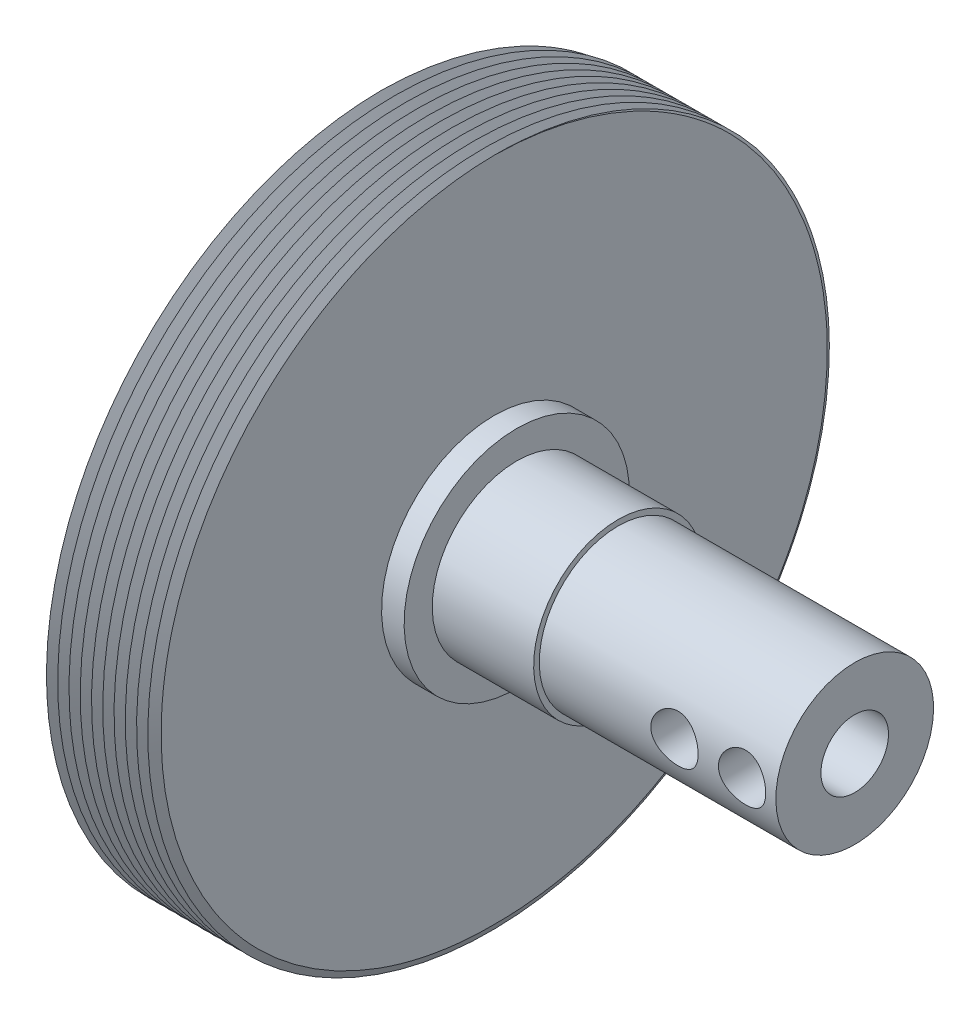
SolidWorks part; units mm, degrees
ref_plane "Front Plane" through (0, 0, 0) normal (0, 0, 1) x (1, 0, 0)
ref_plane "Top Plane" through (0, 0, 0) normal (0, 1, 0) x (1, 0, 0)
ref_plane "Right Plane" through (0, 0, 0) normal (1, 0, 0) x (0, 0, -1)
sketch "Sketch1" plane through (0, 0, 0) normal (0, 0, 1) x (1, 0, 0)
  line L4 (-12.8957, 0) -> (28.1974, 0) construction
  line L5 (0, 0) -> (0, 30)
  line L6 (0, 30) -> (10, 30)
  line L7 (10, 30) -> (10, 10)
  line L8 (10, 10) -> (12, 10)
  line L9 (12, 10) -> (12, 7.5)
  line L10 (12, 7.5) -> (21, 7.5)
  line L13 (42, 7) -> (42, 3)
  line L14 (28.1974, 0) -> (0, 0)
  line L15 (42, 3) -> (30, 3)
  line L16 (30, 3) -> (28.1974, 0)
  line L17 (67.8432, 0) -> (1087.5353, 0) construction
  line L18 (12, 10) -> (11, 10) construction
  line L19 (11, 10) -> (11, 17.5) construction
  line L20 (11, 17.5) -> (10, 17.5) construction
  line L21 (11, 17.5) -> (13, 17.5) construction
  line L22 (13, 17.5) -> (13, 10) construction
  line L23 (13, 10) -> (11, 10) construction
  line L24 (13, 17.5) -> (14, 17.5) construction
  line L25 (14, 17.5) -> (14, 10) construction
  line L26 (14, 10) -> (13, 10) construction
  line L27 (19, 17.5) -> (19, 10) construction
  line L28 (19, 10) -> (20, 10) construction
  line L29 (20, 10) -> (20, 17.5) construction
  line L30 (20, 17.5) -> (19, 17.5) construction
  line L31 (20, 17.5) -> (22, 17.5) construction
  line L32 (22, 17.5) -> (22, 10) construction
  line L33 (22, 10) -> (20, 10) construction
  line L34 (22, 17.5) -> (23, 17.5) construction
  line L35 (23, 17.5) -> (23, 10) construction
  line L36 (23, 10) -> (22, 10) construction
  line L37 (14, 10.5) -> (19, 10.5) construction
  line L38 (14, 7.5) -> (14, 8.5) construction
  line L39 (14, 8.5) -> (19, 8.5) construction
  line L40 (19, 8.5) -> (19, 7.5) construction
  line L41 (14, 9.5) -> (19, 9.5) construction
  line L42 (16.5, 10.5) -> (16.5, 9.5) construction
  line L43 (21, 7.5) -> (21, 7)
  line L44 (21, 7) -> (42, 7)
  line L45 (23, 17.5) -> (29, 17.5) construction
  line L46 (29, 17.5) -> (29, 7) construction
  circle A0 centre (33, 0) radius 2 construction
  circle A1 centre (39, 0) radius 2 construction
  dimension "D21" = 4
  dimension "D1" = 30
  dimension "D2" = 10
  dimension "D3" = 6
  dimension "D4" = 1
  dimension "D5" = 1
  dimension "D6" = 2
  dimension "D7" = 15
  dimension "D8" = 20
  dimension "D9" = 2
  dimension "D10" = 17.5
  dimension "D11" = 10.5
  dimension "D12" = 1
  dimension "D13" = 5
  dimension "D14" = 14
  dimension "D15" = 2
  dimension "D16" = 6
  dimension "D17" = 12
  dimension "D18" = 59
  dimension "D19" = 3
  dimension "D20" = 6
revolve "Revolve1" add sketch "Sketch1" angle 360 about L14
sketch "Sketch2" plane through (0, 0, 0) normal (0, 0, 1) x (1, 0, 0)
  line L0 (0, 30) -> (-0.5, 29.134)
  line L1 (-0.5, 29.134) -> (-1, 30)
  line L2 (-1, 30) -> (-1, 31)
  line L3 (-1, 31) -> (0, 31)
  line L4 (0, 31) -> (0, 30)
  dimension "D1" = 1
  dimension "D2" = 60
  dimension "D3" = 1
sketch "Sketch3" plane through (0, 0, 0) normal (-1, 0, 0) x (0, 0, 1)
  circle A0 centre (0, 0) radius 30 construction
  circle A1 centre (0, 0) radius 30
curve "Helix/Spiral1" pitch 1 height 50 turns 50
sweep "Cut-Sweep1" cut profiles "Sketch2" path "Helix/Spiral1" align with end faces yes
ref_plane "Plane1" through (0, 0, 7) normal (0, 0, 1) x (1, 0, 0)
hole_wizard "M5x0.8 Tapped Hole1" positions "Sketch4" profile "Sketch6" tap size "M5x0.8" standard "ANSI Metric"
sketch "Sketch4" plane through (0, 0, 7) normal (0, 0, 1) x (1, 0, 0)
  point P0 (39, 0)
  point P3 (33, 0)
sketch "Sketch6" plane through (39, 0, 7) normal (1, 0, 0) x (0, -1, 0)
  line L0 (0, 0) -> (0, 8.2618)
  line L1 (0, 8.2618) -> (2.1, 7)
  line L2 (2.1, 7) -> (2.1, 0)
  line L5 (2.1, 0) -> (0, 0)
  line L10 (0, 8.2618) -> (-2.1, 7) construction
  line L11 (0, -6.35) -> (0, 107.95) construction
  dimension "Tap Drill Dia." = 4.2
  dimension "Tap Drill Depth" = 7
  dimension "Drill Angle" = 118
cosmetic thread "Hole Thread1" parameters "D1"=6, "D2"=5
cosmetic thread "Hole Thread2" parameters "D1"=6, "D2"=5
